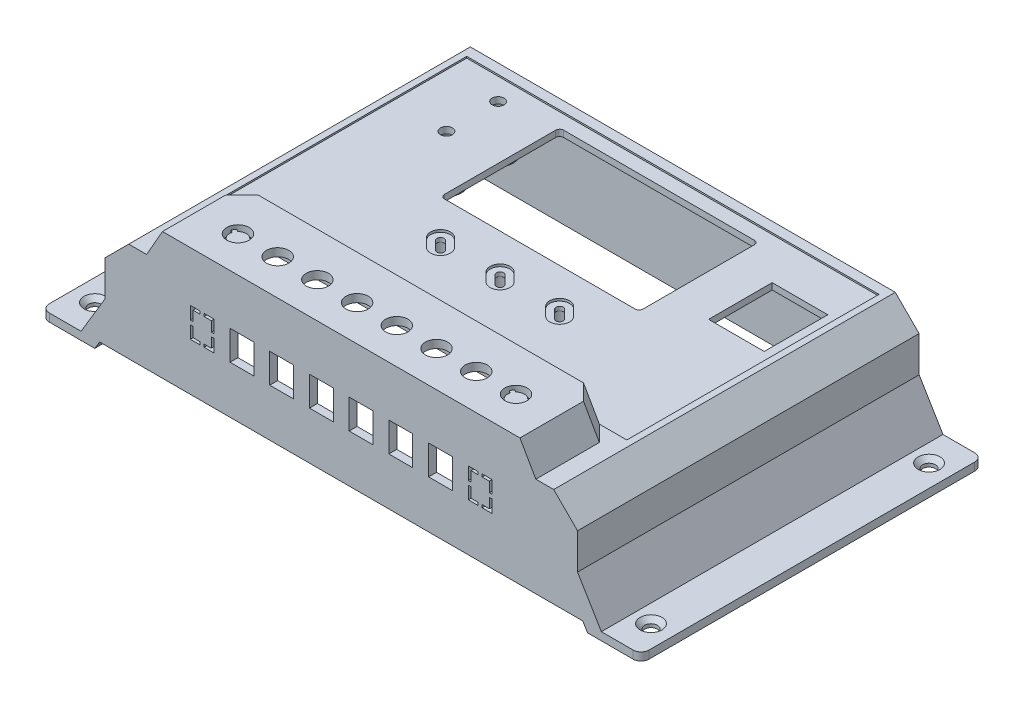
SolidWorks part; units mm, degrees
material "ABS"
ref_plane "Front Plane" through (0, 0, 0) normal (0, 0, 1) x (1, 0, 0)
ref_plane "Top Plane" through (0, 0, 0) normal (0, 1, 0) x (1, 0, 0)
ref_plane "Right Plane" through (0, 0, 0) normal (1, 0, 0) x (0, 0, -1)
sketch "Sketch1" plane through (0, 0, 0) normal (0, 0, 1) x (1, 0, 0)
  line L0 (-65.5, 2) -> (-75.5, 2)
  line L1 (-75.5, 2) -> (-75.5, 0)
  line L2 (-75.5, 0) -> (75.5, 0)
  line L3 (-65.5, 2) -> (-59.5, 12)
  line L4 (-59.5, 12) -> (-59.5, 21)
  line L5 (-59.5, 21) -> (-53.5, 27)
  line L6 (-53.5, 27) -> (53.5, 27)
  line L7 (0, 0) -> (0, 27) construction
  line L8 (59.5, 21) -> (53.5, 27)
  line L9 (59.5, 12) -> (59.5, 21)
  line L10 (65.5, 2) -> (59.5, 12)
  line L11 (75.5, 2) -> (75.5, 0)
  line L12 (65.5, 2) -> (75.5, 2)
  dimension "D1" = 2
  dimension "D2" = 10
  dimension "D3" = 6
  dimension "D4" = 6
  dimension "D5" = 75.5
  dimension "D6" = 10
  dimension "D7" = 27
  dimension "D8" = 6
  dimension "D9" = 45
  dimension "D10" = 9
extrude "MAIN BODY" add sketch "Sketch1" along normal mid plane 86
sketch "Sketch2" plane through (0, 27, 0) normal (0, 1, 0) x (1, 0, 0)
  line L0 (-49, -43) -> (-49, -27)
  line L1 (53.5, -43) -> (-53.5, -43) construction
  line L2 (-49, -27) -> (-45, -23)
  line L3 (-45, -23) -> (45, -23)
  line L4 (-49, -43) -> (49, -43)
  line L5 (0, -43) -> (0, -23) construction
  line L6 (49, -27) -> (45, -23)
  line L7 (49, -43) -> (49, -27)
  dimension "D1" = 49
  dimension "D2" = 20
  dimension "D3" = 4
  dimension "D4" = 4
ref_plane "Plane1" through (0, 34, 0) normal (0, 1, 0) x (1, 0, 0)
sketch "Sketch3" plane through (0, 34, 0) normal (0, 1, 0) x (1, 0, 0)
  line L0 (45, -43) -> (-45, -43)
  line L1 (-49, -43) -> (49, -43) construction
  line L2 (-45, -43) -> (-45, -27)
  line L3 (-45, -27) -> (-41, -23)
  line L4 (-45, -23) -> (45, -23) construction
  line L5 (-41, -23) -> (41, -23)
  line L6 (-49, -27) -> (-45, -23) construction
  line L7 (-45, -27) -> (-49, -27) construction
  line L8 (-49, -43) -> (-49, -27) construction
  line L9 (0, -43) -> (0, -23) construction
  line L10 (45, -27) -> (41, -23)
  line L11 (45, -43) -> (45, -27)
  dimension "D1" = 4
loft "Loft1" add profiles "Sketch2", "Sketch3" connector at (-49, 27, 27) connector at (-45, 34, 27)
shell "Shell1" thickness 2 removed face at (0, 0, 0)
sketch "Sketch6" plane through (0, 0, 0) normal (0, 0, 1) x (1, 0, 0)
  line L0 (60.8352, 2) -> (-60.8352, 2)
  line L1 (-60.8352, 2) -> (-62.0352, 0)
  line L2 (-75.5, 0) -> (75.5, 0) construction
  line L3 (-62.0352, 0) -> (62.0352, 0)
  line L5 (-59.5, 12) -> (-65.5, 2) construction
  line L6 (0, 0) -> (0, 2) construction
  line L8 (-61.4352, 1) -> (-64.8652, 3.058) construction
  line L9 (61.4352, 1) -> (64.8652, 3.058) construction
  line L10 (60.8352, 2) -> (62.0352, 0)
  dimension "D1" = 2
  dimension "D2" = 4
extrude "Cut-Extrude2" cut sketch "Sketch6" against normal through all both and the other way through all
hole_wizard "M3 Clearance Hole1" positions "Sketch7" profile "Sketch8" hole size "M3" standard "ANSI Metric" end condition through all
sketch "Sketch7" plane through (0, 2, 0) normal (0, 1, 0) x (1, 0, 0)
  line L0 (-75.5, -43) -> (-75.5, 43) construction
  point P0 (-70, 35)
  dimension "D1" = 5.5
  dimension "D2" = 35
sketch "Sketch8" plane through (-70, 2, -35) normal (1, 0, 0) x (0, 0, 1)
  line L0 (0, 0) -> (0, 2)
  line L1 (0, 2) -> (1.6, 2)
  line L2 (1.6, 2) -> (1.6, 1.15)
  line L3 (1.6, 1.15) -> (2.75, 0)
  line L5 (2.75, 0) -> (0, 0)
  line L6 (-1.6, 1.15) -> (-2.75, 0) construction
  line L11 (0, -6.35) -> (0, 107.95) construction
  dimension "Thru Hole Dia." = 3.2
  dimension "Thru Hole Depth" = 2
  dimension "Near C'Sink Dia." = 5.5
  dimension "Near C'Sink Angle" = 90
mirror "Mirror1" about plane through (0, 0, 0) normal (0, 0, 1) of "M3 Clearance Hole1"
mirror "Mirror2" about plane through (0, 0, 0) normal (1, 0, 0) of "Mirror1", "M3 Clearance Hole1"
ref_plane "Plane2" through (0, 4, 0) normal (0, 1, 0) x (1, 0, 0)
ref_plane "Plane3" through (0, 10, 0) normal (0, 1, 0) x (1, 0, 0)
sketch "Sketch9" plane through (0, 4, 0) normal (0, -1, 0) x (1, 0, 0)
  circle A0 centre (-59.5, 32.5) radius 2.5
  circle A1 centre (-59.5, 32.5) radius 1
  dimension "D1" = 5
  dimension "D2" = 2
  dimension "D4" = 32.5
  dimension "D3" = 59.5
extrude "Boss-Extrude3" add sketch "Sketch9" against normal up to next
sketch "Sketch12" plane through (0, 10, 0) normal (0, -1, 0) x (1, 0, 0)
  circle A0 centre (-52.5, 36) radius 2.5
  circle A1 centre (-52.5, 36) radius 1
  circle A2 centre (-59.5, 32.5) radius 2.5 construction
  circle A3 centre (-59.5, 32.5) radius 1 construction
  dimension "D1" = 52.5
  dimension "D2" = 36
extrude "Boss-Extrude4" add sketch "Sketch12" against normal up to next
mirror "Mirror3" about plane through (0, 0, 0) normal (1, 0, 0) of "Boss-Extrude4", "Boss-Extrude3"
mirror "Mirror4" about plane through (0, 0, 0) normal (0, 0, 1) of "Mirror3", "Boss-Extrude3"
sketch "Sketch10" plane through (0, 27, 0) normal (0, 1, 0) x (1, 0, 0)
  line L0 (0, 43) -> (0, 22) construction
  line L1 (-25, 37) -> (25, 37)
  line L2 (-25, 37) -> (-25, 7)
  line L3 (-25, 7) -> (25, 7)
  line L4 (25, 37) -> (25, 7)
  line L5 (-25, 37) -> (25, 7) construction
  line L6 (-25, 7) -> (25, 37) construction
  line L7 (53.5, 43) -> (-53.5, 43) construction
  point P0 (0, 22)
  dimension "D1" = 50
  dimension "D2" = 30
  dimension "D3" = 6
extrude "Cut-Extrude3" cut sketch "Sketch10" against normal up to next
sketch "Sketch11" plane through (0, 27, 0) normal (0, 1, 0) x (1, 0, 0)
  line L0 (42.5, 22) -> (25, 22) construction
  line L1 (35.5, 30) -> (49.5, 30)
  line L2 (35.5, 30) -> (35.5, 14)
  line L3 (35.5, 14) -> (49.5, 14)
  line L4 (49.5, 30) -> (49.5, 14)
  line L5 (35.5, 30) -> (49.5, 14) construction
  line L6 (35.5, 14) -> (49.5, 30) construction
  line L7 (25, 7) -> (25, 37) construction
  line L8 (53.5, -43) -> (53.5, 43) construction
  point P0 (42.5, 22)
  dimension "D1" = 14
  dimension "D2" = 16
  dimension "D3" = 4
extrude "Cut-Extrude4" cut sketch "Sketch11" against normal up to next
sketch "Sketch13" plane through (0, 27, 0) normal (0, 1, 0) x (1, 0, 0)
  line L0 (-1.0607, -1.9393) -> (1.0607, -4.0607) construction
  line L1 (0.7071, -0.1716) -> (2.8284, -2.2929)
  line L2 (-2.8284, -3.7071) -> (-0.7071, -5.8284)
  line L3 (0, 0) -> (0, -3) construction
  line L4 (-25, 7) -> (25, 7) construction
  arc A0 (0.7071, -0.1716) -> (-2.8284, -3.7071) centre (-1.0607, -1.9393) ccw
  arc A1 (-0.7071, -5.8284) -> (2.8284, -2.2929) centre (1.0607, -4.0607) ccw
  point P2 (0, -3)
  dimension "D2" = 2.5
  dimension "D1" = 10
  dimension "D3" = 45
  dimension "D4" = 3
extrude "Cut-Extrude5" cut sketch "Sketch13" against normal through all
sketch "Sketch27" plane through (0, 25, 0) normal (0, -1, 0) x (1, 0, 0)
  line L0 (0.7071, 0.1716) -> (2.8284, 2.2929) construction
  line L1 (-0.7071, 5.8284) -> (-2.8284, 3.7071) construction
  line L2 (0.7071, 0.1716) -> (2.8284, 2.2929)
  line L3 (-0.7071, 5.8284) -> (-2.8284, 3.7071)
  line L4 (-0.4243, 1.3029) -> (1.6971, 3.4243)
  line L5 (0.4243, 4.6971) -> (-1.6971, 2.5757)
  arc A0 (-2.8284, 3.7071) -> (0.7071, 0.1716) centre (-1.0607, 1.9393) ccw construction
  arc A1 (2.8284, 2.2929) -> (-0.7071, 5.8284) centre (1.0607, 4.0607) ccw construction
  arc A2 (-2.8284, 3.7071) -> (0.7071, 0.1716) centre (-1.0607, 1.9393) ccw
  arc A3 (2.8284, 2.2929) -> (-0.7071, 5.8284) centre (1.0607, 4.0607) ccw
  arc A4 (1.6971, 3.4243) -> (0.4243, 4.6971) centre (1.0607, 4.0607) ccw
  arc A5 (-1.6971, 2.5757) -> (-0.4243, 1.3029) centre (-1.0607, 1.9393) ccw
  dimension "D1" = 1.6
extrude "Boss-Extrude9" add sketch "Sketch27" against normal blind 1
sketch "Sketch26" plane through (0, 25, 0) normal (0, -1, 0) x (1, 0, 0)
  line L0 (-1.0607, 1.9393) -> (1.0607, 4.0607) construction
  circle A0 centre (0, 3) radius 3.4
  arc A1 (-0.7071, 5.8284) -> (2.8284, 2.2929) centre (1.0607, 4.0607) ccw construction
  circle A2 centre (0, 3) radius 2.4
  arc A3 (-1.6971, 2.5757) -> (-0.4243, 1.3029) centre (-1.0607, 1.9393) ccw construction
  dimension "D1" = 6.8
  dimension "D2" = 1
extrude "Boss-Extrude10" add sketch "Sketch26" along normal blind 5.5
sketch "Sketch28" plane through (0, 19.5, 0) normal (0, -1, 0) x (-1, 0, 0)
  line L1 (0.5, -6.4) -> (-0.5, -6.4)
  line L2 (0.5, -6.4) -> (0.5, 0.4)
  line L3 (0.5, 0.4) -> (-0.5, 0.4)
  line L4 (-0.5, -6.4) -> (-0.5, 0.4)
  line L5 (0.5, -6.4) -> (-0.5, 0.4) construction
  line L6 (0.5, 0.4) -> (-0.5, -6.4) construction
  arc A0 (-1.6971, -4.6971) -> (1.6971, -1.3029) centre (0, -3) ccw construction
  circle A1 centre (0, -3) radius 3.4 construction
  point P0 (0, -3)
  dimension "D1" = 1
extrude "Cut-Extrude10" cut sketch "Sketch28" against normal up to surface (5.5 mm away) up to face at (-52.0858, 25, 36)
pattern_linear "LPattern1" count 2 spacing 15 along (1, 0, 0) count 2 spacing 15 along (-1, 0, 0) of "Cut-Extrude5", "Boss-Extrude9", "Boss-Extrude10", "Cut-Extrude10" pattern seed only yes
sketch "Sketch14" plane through (0, 27, 0) normal (0, 1, 0) x (1, 0, 0)
  line L0 (-38.5, 35) -> (-38.5, 22) construction
  line L1 (53.5, 43) -> (-53.5, 43) construction
  line L2 (-75.5, -43) -> (-75.5, 43) construction
  circle A0 centre (-38.5, 35) radius 1.5
  circle A1 centre (-38.5, 22) radius 1.5
  dimension "D4" = 3
  dimension "D1" = 13
  dimension "D2" = 38.5
  dimension "D3" = 8
  dimension "D5" = 37
extrude "Cut-Extrude6" cut sketch "Sketch14" against normal through all
sketch "Sketch15" plane through (0, 34, 0) normal (0, 1, 0) x (1, 0, 0)
  line L0 (-45, -43) -> (45, -43) construction
  circle A0 centre (-5, -34) radius 2.8
  dimension "D2" = 9
  dimension "D3" = 5.6
  dimension "D1" = 5
extrude "Cut-Extrude7" cut sketch "Sketch15" against normal through all
sketch "Sketch16" plane through (0, 0, 43) normal (0, 0, 1) x (1, 0, 0)
  line L0 (-2.2, 34) -> (-7.8, 34) construction
  line L1 (-8, 21.4) -> (-2, 21.4)
  line L2 (-8, 21.4) -> (-8, 14)
  line L3 (-8, 14) -> (-2, 14)
  line L4 (-2, 21.4) -> (-2, 14)
  line L5 (-8, 21.4) -> (-2, 14) construction
  line L6 (-8, 14) -> (-2, 21.4) construction
  line L7 (-5, 34) -> (-5, 17.7) construction
  line L9 (60.8352, 2) -> (-60.8352, 2) construction
  point P0 (-5, 17.7)
  dimension "D1" = 6
  dimension "D2" = 7.4
  dimension "D3" = 12
extrude "Cut-Extrude8" cut sketch "Sketch16" against normal up to next
pattern_linear "LPattern2" count 4 spacing 10 along (-1, 0, 0) of "Cut-Extrude7", "Cut-Extrude8"
mirror "Mirror5" about plane through (0, 0, 0) normal (1, 0, 0) of "LPattern2", "Cut-Extrude7"
sketch "Sketch17" plane through (0, 25, 0) normal (0, -1, 0) x (1, 0, 0)
  circle A0 centre (-38.5, -22) radius 3.75
  circle A1 centre (-38.5, -35) radius 3.75
  circle A4 centre (-38.5, -22) radius 1.8
  circle A5 centre (-38.5, -35) radius 1.8
  dimension "D1" = 7.5
  dimension "D2" = 3.6
extrude "Boss-Extrude5" add sketch "Sketch17" along normal blind 10
sketch "Sketch18" plane through (0, 0, 43) normal (0, 0, 1) x (1, 0, 0)
  line L0 (-35, 14) -> (-35, 21.4)
  line L1 (-38, 14) -> (-32, 14) construction
  line L2 (-32, 21.4) -> (-38, 21.4) construction
  line L3 (35, 14) -> (35, 21.4)
  line L4 (38, 14) -> (32, 14) construction
  line L5 (32, 21.4) -> (38, 21.4) construction
extrude "Extrude-Thin1" add sketch "Sketch18" against normal up to surface (2 mm away) thin up to face at (15, 17.7, 41) thin type mid plane wall 1
sketch "Sketch19" plane through (0, 0, 43) normal (0, 0, 1) x (1, 0, 0)
  line L0 (-38, 17.7) -> (-32, 17.7)
  line L1 (-38, 21.4) -> (-38, 14) construction
  line L2 (-32, 14) -> (-32, 21.4) construction
  line L3 (32, 17.7) -> (38, 17.7)
  line L4 (32, 14) -> (32, 21.4) construction
  line L5 (38, 21.4) -> (38, 14) construction
extrude "Extrude-Thin2" add sketch "Sketch19" against normal up to surface (2 mm away) thin up to face at (33.25, 17.7, 41) thin type mid plane wall 1
sketch "Sketch20" plane through (0, 0, 43) normal (0, 0, 1) x (1, 0, 0)
  line L0 (-35.5, 18.2) -> (-34.5, 17.2) construction
  line L1 (-37.3, 20.7) -> (-32.7, 20.7)
  line L2 (-37.3, 20.7) -> (-37.3, 14.7)
  line L3 (-37.3, 14.7) -> (-32.7, 14.7)
  line L4 (-32.7, 20.7) -> (-32.7, 14.7)
  line L5 (-37.3, 20.7) -> (-32.7, 14.7) construction
  line L6 (-37.3, 14.7) -> (-32.7, 20.7) construction
  line L7 (34.5, 18.2) -> (35.5, 17.2) construction
  line L8 (32.7, 20.7) -> (37.3, 20.7)
  line L9 (32.7, 20.7) -> (32.7, 14.7)
  line L10 (32.7, 14.7) -> (37.3, 14.7)
  line L11 (37.3, 20.7) -> (37.3, 14.7)
  line L12 (32.7, 20.7) -> (37.3, 14.7) construction
  line L13 (32.7, 14.7) -> (37.3, 20.7) construction
  line L14 (-38, 21.4) -> (-38, 18.2) construction
  line L15 (-32, 21.4) -> (-34.5, 21.4) construction
  point P0 (-35, 17.7)
  point P10 (35, 17.7)
  dimension "D1" = 0.7
  dimension "D2" = 0.7
extrude "Boss-Extrude6" add sketch "Sketch20" against normal up to surface (2 mm away) up to face at (36.75, 19.8, 41)
sketch "Sketch21" plane through (0, 32, 0) normal (0, -1, 0) x (1, 0, 0)
  line L0 (-35, 34) -> (-35, 36.8)
  circle A0 centre (-35, 34) radius 2.8 construction
extrude "Extrude-Thin3" add sketch "Sketch21" against normal blind 1 thin thin type mid plane wall 1
pattern_circular "CirPattern1" count 3 over 360 about axis through (-35, 0, 34) along (0, 1, 0) of "Extrude-Thin3" reverse direction yes
sketch "Sketch22" plane through (0, 32, 0) normal (0, -1, 0) x (-1, 0, 0)
  circle A0 centre (35, -34) radius 2.1
  circle A1 centre (35, -34) radius 2.8 construction
  dimension "D1" = 0.7
extrude "Boss-Extrude7" add sketch "Sketch22" against normal up to surface (1 mm away)
mirror "Mirror6" about plane through (0, 0, 0) normal (1, 0, 0) of "Boss-Extrude7", "Extrude-Thin3", "CirPattern1"
sketch "Sketch23" plane through (0, 0, -43) normal (0, 0, -1) x (-1, 0, 0)
  line L0 (-60.8352, 2) -> (60.8352, 2) construction
  line L1 (-37.5, 9.8) -> (-43.3, 9.8)
  line L2 (-37.5, 9.8) -> (-37.5, 17.1)
  line L3 (-37.5, 17.1) -> (-43.3, 17.1)
  line L4 (-43.3, 9.8) -> (-43.3, 17.1)
  line L5 (-37.5, 9.8) -> (-43.3, 17.1) construction
  line L6 (-37.5, 17.1) -> (-43.3, 9.8) construction
  line L7 (-75.5, 0) -> (-75.5, 2) construction
  point P0 (-40.4, 13.45)
  dimension "D1" = 7.3
  dimension "D2" = 5.8
  dimension "D3" = 7.8
  dimension "D4" = 32.2
extrude "Cut-Extrude9" cut sketch "Sketch23" against normal up to next
sketch "Sketch24" plane through (0, 0, -43) normal (0, 0, -1) x (-1, 0, 0)
  line L0 (-40.4, 17.1) -> (-40.4, 9.8)
  line L1 (-37.5, 17.1) -> (-43.3, 17.1) construction
  line L2 (-43.3, 9.8) -> (-37.5, 9.8) construction
  line L3 (-37.5, 13.45) -> (-43.3, 13.45)
  line L4 (-37.5, 9.8) -> (-37.5, 17.1) construction
  line L5 (-43.3, 17.1) -> (-43.3, 9.8) construction
extrude "Extrude-Thin4" add sketch "Sketch24" against normal blind 1 thin thin type mid plane wall 1
sketch "Sketch25" plane through (0, 0, -43) normal (0, 0, -1) x (-1, 0, 0)
  line L0 (-43.3, 17.1) -> (-43.3, 13.95) construction
  line L1 (-42.3, 16.1) -> (-38.5, 16.1)
  line L2 (-42.3, 16.1) -> (-42.3, 10.8)
  line L3 (-42.3, 10.8) -> (-38.5, 10.8)
  line L4 (-38.5, 16.1) -> (-38.5, 10.8)
  line L5 (-40.9, 17.1) -> (-43.3, 17.1) construction
  line L6 (-39.9, 12.95) -> (-40.9, 13.95) construction
  line L7 (-42.3, 10.8) -> (-38.5, 16.1) construction
  point P12 (-40.4, 13.45)
  dimension "D1" = 1
  dimension "D2" = 1
extrude "Boss-Extrude8" add sketch "Sketch25" against normal up to surface (1 mm away) up to face at (40.4, 13.45, -42)
sketch "Sketch29" plane through (0, 27, 0) normal (0, 1, 0) x (1, 0, 0)
  line L0 (41, -23) -> (-41, -23) construction
  line L1 (-51.9, 40.5) -> (51.9, 40.5)
  line L2 (-51.9, 40.5) -> (-51.9, -23)
  line L3 (-51.9, -23) -> (51.9, -23)
  line L4 (51.9, 40.5) -> (51.9, -23)
  line L5 (53.5, 43) -> (-53.5, 43) construction
  line L6 (-53.5, -43) -> (-53.5, 43) construction
  line L7 (0, 40.5) -> (0, 43) construction
  dimension "D1" = 2.5
  dimension "D2" = 1.6
extrude "Cut-Extrude11" cut sketch "Sketch29" against normal blind 0.4
fillet "Fillet1" radius 1 4 edges at (25, 25.8, -7) (-25, 25.8, -7) (-25, 25.8, -37) (25, 25.8, -37)
fillet "Fillet2" radius 2 4 edges at (75.5, 1, -43) (75.5, 1, 43) (-75.5, 1, 43) (-75.5, 1, -43)
